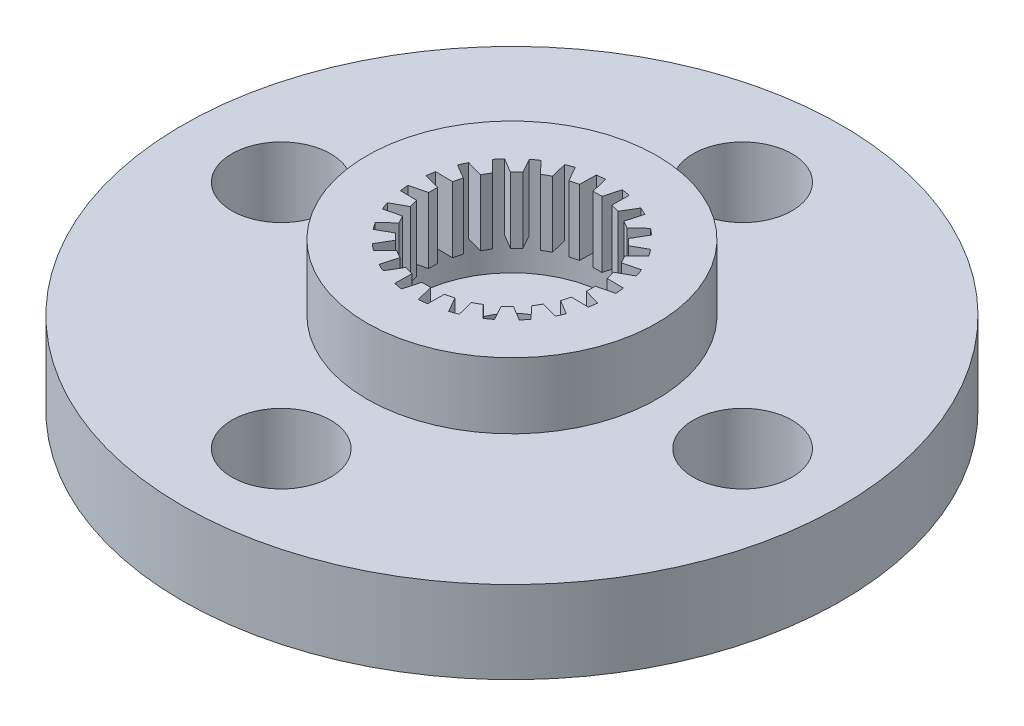
SolidWorks part; units mm, degrees
ref_plane "前视基准面" through (0, 0, 0) normal (0, 0, 1) x (1, 0, 0)
ref_plane "上视基准面" through (0, 0, 0) normal (0, 1, 0) x (1, 0, 0)
ref_plane "右视基准面" through (0, 0, 0) normal (1, 0, 0) x (0, 0, -1)
sketch "草图4" plane through (0, 0, 0) normal (0, 1, 0) x (1, 0, 0)
  circle A0 centre (0, 0) radius 10
  dimension "D1" = 20
extrude "凸台-拉伸2" add sketch "草图4" along normal blind 2.5
ref_plane "基准面7" through (0, 2.5, 0) normal (0, 1, 0) x (1, 0, 0)
sketch "草图6" plane through (0, 2.5, 0) normal (0, 1, 0) x (1, 0, 0)
  circle A0 centre (0, 0) radius 7 construction
  circle A1 centre (0, 7) radius 1.5
  circle A2 centre (0, 0) radius 1.5
  circle A3 centre (7, 0) radius 1.5
  circle A4 centre (-7, 0) radius 1.5
  circle A5 centre (0, -7) radius 1.5
  dimension "D1" = 3
  dimension "D2" = 3
  dimension "D3" = 3
  dimension "D4" = 3
  dimension "D5" = 3
  dimension "D6" = 14
extrude "切除-拉伸9" cut sketch "草图6" against normal blind 2.5
sketch "草图7" plane through (0, 2.5, 0) normal (0, 1, 0) x (1, 0, 0)
  circle A0 centre (0, 0) radius 4.4
  dimension "D1" = 8.8
extrude "凸台-拉伸3" add sketch "草图7" along normal blind 2
ref_plane "基准面8" through (0, 4.5, 0) normal (0, 1, 0) x (1, 0, 0)
sketch "草图8" plane through (0, 4.5, 0) normal (0, 1, 0) x (1, 0, 0)
  circle A0 centre (0, 0) radius 3
  dimension "D1" = 6
extrude "切除-拉伸10" cut sketch "草图8" against normal blind 3
ref_axis "基准轴1" through (0, 1.5, 0) along (0, 1, 0)
sketch "草图14" plane through (0, 4.5, 0) normal (0, 1, 0) x (1, 0, 0)
  line L0 (2.9769, -0.3715) -> (2.4958, -0.2354)
  line L1 (2.4958, -0.2354) -> (2.4958, 0.0323)
  line L2 (2.4958, 0.0323) -> (2.9958, 0.1588)
  arc A0 (2.9769, -0.3715) -> (2.9958, 0.1588) centre (0, 0) ccw
  dimension "D3" = 3
  dimension "D1" = 30
  dimension "D2" = 0.5
  dimension "0.5" = 0.5
extrude "凸台-拉伸5" add sketch "草图14" against normal blind 2
pattern_circular "阵列(圆周)1" count 24 over 360 about axis through (0, 4.5, 0) along (0, 1, 0) of "凸台-拉伸5"
